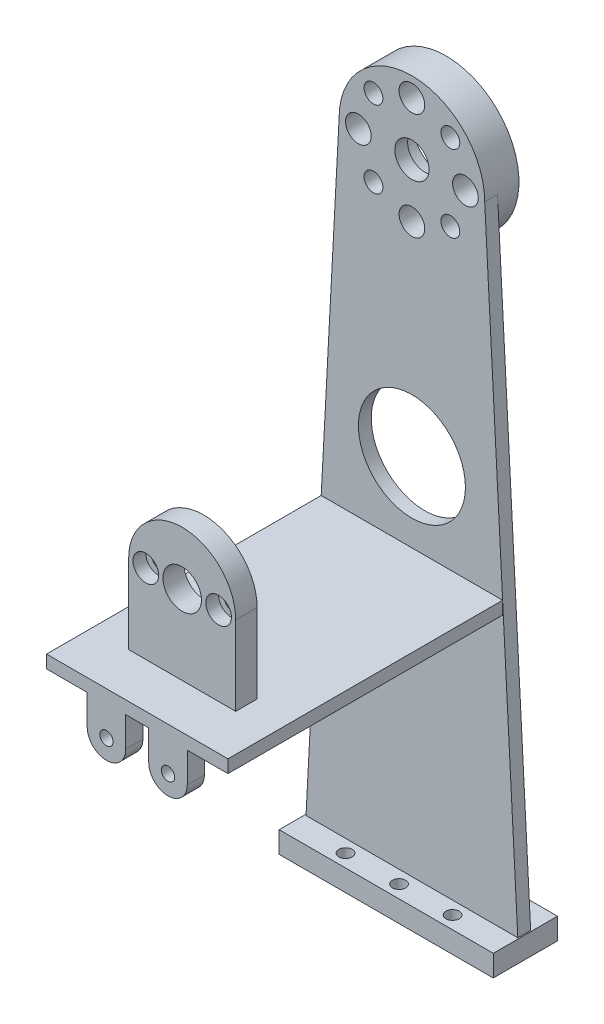
SolidWorks part; units mm, degrees
ref_plane "Front Plane" through (0, 0, 0) normal (0, 0, 1) x (1, 0, 0)
ref_plane "Top Plane" through (0, 0, 0) normal (0, 1, 0) x (1, 0, 0)
ref_plane "Right Plane" through (0, 0, 0) normal (1, 0, 0) x (0, 0, -1)
sketch "Sketch1" plane through (0, 0, 0) normal (0, 0, 1) x (1, 0, 0)
  line L0 (-25, 0) -> (25, 0)
  line L1 (0, 0) -> (0, 150) construction
  line L2 (-17, 150) -> (-25, 0)
  line L3 (25, 0) -> (17, 150)
  line L4 (0, 150) -> (0, 90) construction
  circle A0 centre (0, 150) radius 4
  arc A1 (-17, 150) -> (17, 150) centre (0, 150) cw
  circle A2 centre (0, 90) radius 12.5
  point P4 (0, 0)
extrude "Boss-Extrude1" add sketch "Sketch1" along normal blind 3
sketch "Sketch2" plane through (0, 0, 0) normal (0, 0, -1) x (-1, 0, 0)
  circle A0 centre (0, 150) radius 17
  circle A1 centre (0, 150) radius 8
extrude "Boss-Extrude2" add sketch "Sketch2" along normal blind 5
sketch "Sketch3" plane through (0, 0, 3) normal (0, 0, 1) x (1, 0, 0)
  line L0 (0, 150) -> (8.9803, 158.9803) construction
  circle A0 centre (0, 150) radius 12.5 construction
  circle A1 centre (-12.5, 150) radius 1.55
  circle A2 centre (0, 162.5) radius 1.55
  circle A3 centre (12.5, 150) radius 1.55
  circle A4 centre (0, 137.5) radius 1.55
  circle A5 centre (0, 150) radius 12.7 construction
  circle A6 centre (8.9803, 158.9803) radius 1
  circle A7 centre (8.9803, 141.0197) radius 1
  circle A8 centre (-8.9803, 141.0197) radius 1
  circle A9 centre (-8.9803, 158.9803) radius 1
  point P14 (0, 150)
  point P24 (0, 150)
  dimension "D1" = 4
  dimension "D2" = 4
extrude "Cut-Extrude1" cut sketch "Sketch3" against normal blind 8
sketch "Sketch4" plane through (0, 0, 3) normal (0, 0, 1) x (1, 0, 0)
  circle A0 centre (-12.5, 150) radius 3
  circle A1 centre (0, 162.5) radius 3
  circle A2 centre (12.5, 150) radius 3
  circle A3 centre (0, 137.5) radius 3
  circle A4 centre (-8.9803, 158.9803) radius 2.2
  circle A5 centre (8.9803, 158.9803) radius 2.2
  circle A6 centre (8.9803, 141.0197) radius 2.2
  circle A7 centre (-8.9803, 141.0197) radius 2.2
  point P12 (0, 150)
  point P22 (0, 150)
  dimension "D1" = 4
  dimension "D2" = 4
extrude "Cut-Extrude2" cut sketch "Sketch4" against normal blind 4.5
sketch "Sketch5" plane through (0, 0, 0) normal (0, -1, 0) x (1, 0, 0)
  line L3 (-25, -6) -> (-25, 9)
  line L5 (25, -6) -> (25, 9)
  line L7 (-25, 9) -> (25, 9)
  line L8 (25, -6) -> (-25, -6)
  circle A0 centre (-12.5, 6) radius 1.55
  circle A1 centre (0, 6) radius 1.55
  circle A2 centre (12.5, 6) radius 1.55
  circle A3 centre (0, -3) radius 1.55
  circle A4 centre (-12.5, -3) radius 1.55
  circle A5 centre (12.5, -3) radius 1.55
extrude "Boss-Extrude3" add sketch "Sketch5" against normal blind 5
sketch "Sketch8" plane through (0, 0, 3) normal (0, 0, 1) x (1, 0, 0)
  line L0 (-21.1867, 71.5) -> (21.1867, 71.5) construction
  line L2 (25, 0) -> (17, 150) construction
  point P3 (0, 71.5)
ref_plane "Plane3" through (0, 71.5, 0) normal (0, -1, 0) x (1, 0, 0)
sketch "Sketch9" plane through (0, 71.5, 0) normal (0, -1, 0) x (1, 0, 0)
  line L0 (-21.1867, 3) -> (21.1867, 3)
  line L1 (-21.1867, 3) -> (21.1867, 3) construction
  line L2 (21.1867, 3) -> (21.1867, 67.15)
  line L3 (21.1867, 67.15) -> (-21.1867, 67.15)
  line L4 (-21.1867, 67.15) -> (-21.1867, 3)
extrude "Boss-Extrude6" add sketch "Sketch9" along normal blind 3
sketch "Sketch10" plane through (0, 71.5, 0) normal (0, 1, 0) x (1, 0, 0)
  line L0 (0, -67.15) -> (0, -51.65) construction
  line L1 (21.1867, -67.15) -> (-21.1867, -67.15) construction
  line L2 (-21.1867, -51.65) -> (21.1867, -51.65) construction
  line L3 (21.1867, -3) -> (21.1867, -67.15) construction
  point P10 (0, -51.65)
ref_plane "Plane4" through (0, 0, 51.65) normal (0, 0, 1) x (1, 0, 0)
sketch "Sketch11" plane through (0, 0, 51.65) normal (0, 0, 1) x (1, 0, 0)
  line L0 (-8.5, 90) -> (8.5, 90) construction
  line L2 (-12.5, 90) -> (-12.5, 71.5)
  line L3 (-21.1867, 71.5) -> (21.1867, 71.5) construction
  line L4 (-12.5, 71.5) -> (12.5, 71.5)
  line L5 (12.5, 71.5) -> (12.5, 90)
  circle A0 centre (-8.5, 90) radius 1.55
  circle A1 centre (8.5, 90) radius 1.55
  arc A2 (-12.5, 90) -> (12.5, 90) centre (0, 90) cw
  circle A3 centre (0, 90) radius 12.5 construction
  circle A4 centre (0, 90) radius 4.5
  point P4 (0, 90)
extrude "Boss-Extrude7" add sketch "Sketch11" along normal blind 5
sketch "Sketch12" plane through (0, 0, 67.15) normal (0, 0, 1) x (1, 0, 0)
  line L0 (-21.1867, 68.5) -> (-7.1867, 68.5) construction
  line L1 (-21.1867, 68.5) -> (21.1867, 68.5) construction
  line L2 (21.1867, 68.5) -> (7.1867, 68.5) construction
  line L3 (-7.1867, 68.5) -> (-7.1867, 61.5) construction
  line L4 (7.1867, 68.5) -> (7.1867, 61.5) construction
  line L11 (-11.6867, 61.5) -> (-11.6867, 68.5)
  line L12 (-11.6867, 68.5) -> (-2.6867, 68.5)
  line L13 (21.1867, 68.5) -> (-21.1867, 68.5) construction
  line L14 (-2.6867, 68.5) -> (-2.6867, 61.5)
  line L15 (2.6867, 61.5) -> (2.6867, 68.5)
  line L16 (2.6867, 68.5) -> (11.6867, 68.5)
  line L17 (11.6867, 68.5) -> (11.6867, 61.5)
  arc A0 (-11.6867, 61.5) -> (-2.6867, 61.5) centre (-7.1867, 61.5) ccw
  arc A1 (2.6867, 61.5) -> (11.6867, 61.5) centre (7.1867, 61.5) ccw
  circle A2 centre (-7.1867, 61.5) radius 1.55
  circle A3 centre (7.1867, 61.5) radius 1.55
extrude "Boss-Extrude8" add sketch "Sketch12" against normal blind 4
sketch "Sketch13" plane through (0, 0, 56.65) normal (0, 0, 1) x (1, 0, 0)
  circle A0 centre (-8.5, 90) radius 3
  circle A1 centre (8.5, 90) radius 3
extrude "Cut-Extrude3" cut sketch "Sketch13" against normal blind 3
